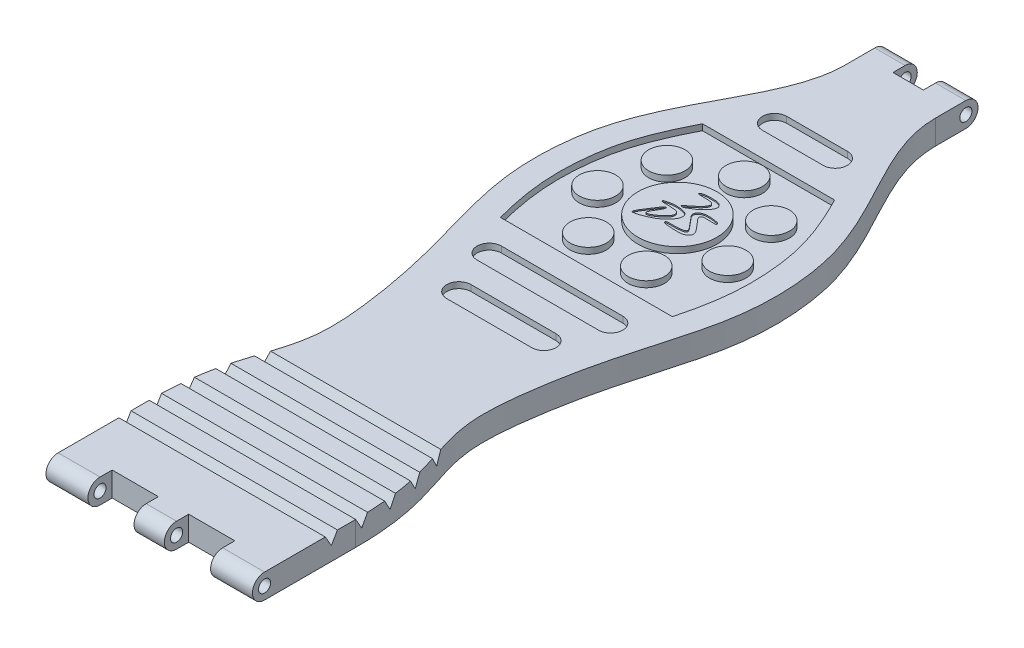
SolidWorks part; units mm, degrees
ref_plane "Front Plane" through (0, 0, 0) normal (0, 0, 1) x (1, 0, 0)
ref_plane "Top Plane" through (0, 0, 0) normal (0, 1, 0) x (1, 0, 0)
ref_plane "Right Plane" through (0, 0, 0) normal (1, 0, 0) x (0, 0, -1)
other "Configuration Table"
sketch "Sketch1" plane through (0, 0, 0) normal (0, 1, 0) x (1, 0, 0)
  line L0 (0, 0) -> (0, 152.4) construction
  line L2 (-21.59, 0) -> (21.59, 0)
  line L3 (-21.59, 0) -> (-21.59, 19.05)
  line L4 (-21.59, 19.05) -> (21.59, 19.05)
  line L5 (21.59, 0) -> (21.59, 19.05)
  line L6 (-21.59, 0) -> (21.59, 19.05) construction
  line L7 (-21.59, 19.05) -> (21.59, 0) construction
  line L8 (-9.525, 152.4) -> (9.525, 152.4)
  line L9 (-9.525, 152.4) -> (-9.525, 158.75)
  line L10 (-9.525, 158.75) -> (9.525, 158.75)
  line L11 (9.525, 152.4) -> (9.525, 158.75)
  line L12 (-9.525, 152.4) -> (9.525, 158.75) construction
  line L13 (-9.525, 158.75) -> (9.525, 152.4) construction
  spline S0 degree 3 poles (-9.525, 152.4) (-9.525, 140.7805) (-22.9495, 127.2801) (-26.9071, 91.7166) (-18.6052, 80.0483) (-14.4166, 41.5339) (-21.59, 36.242) (-21.59, 19.05) knots 0 0 0 0 0.318102 0.39652 0.741104 0.805759 1 1 1 1
  spline S1 degree 3 poles (9.525, 152.4) (9.525, 140.7805) (22.9495, 127.2801) (26.9071, 91.7166) (18.6052, 80.0483) (14.4166, 41.5339) (21.59, 36.242) (21.59, 19.05) knots 0 0 0 0 0.318102 0.39652 0.741104 0.805759 1 1 1 1
  point P7 (0, 9.525)
  point P12 (0, 155.575)
  dimension "D1" = 152.4
  dimension "D2" = 43.18
  dimension "D3" = 19.05
  dimension "D4" = 19.05
  dimension "D5" = 6.35
extrude "Boss-Extrude1" add sketch "Sketch1" against normal blind 5.08 contours S1 L8 S0 L4 | L2 L5 L4 L3 | L8 L11 L10 L9 region at (0, 0, -9.525) region at (0, 0, -84.0947) region at (0, 0, -155.575)
sketch "Sketch2" plane through (-21.59, 0, 0) normal (-1, 0, 0) x (0, 0, 1)
  line L0 (0, -5.08) -> (0, 0) construction
  circle A0 centre (0, -2.54) radius 2.54
extrude "Boss-Extrude2" add sketch "Sketch2" against normal up to surface (43.18 mm away) up to face at (21.59, -2.54, -9.525)
sketch "Sketch3" plane through (-9.525, 0, 0) normal (-1, 0, 0) x (0, 0, 1)
  line L0 (-158.75, -5.08) -> (-158.75, 0) construction
  circle A0 centre (-158.75, -2.54) radius 2.54
extrude "Boss-Extrude3" add sketch "Sketch3" against normal up to surface (19.05 mm away) up to face at (9.525, -2.54, -155.575)
sketch "Sketch4" plane through (-9.525, 0, 0) normal (-1, 0, 0) x (0, 0, 1)
  circle A0 centre (-158.75, -2.54) radius 1.27
  dimension "D1" = 2.54
extrude "Cut-Extrude1" cut sketch "Sketch4" against normal up to surface (19.05 mm away) up to face at (9.525, -2.54, -156.21)
sketch "Sketch5" plane through (-21.59, 0, 0) normal (-1, 0, 0) x (0, 0, 1)
  circle A0 centre (0, -2.54) radius 1.27
  dimension "D1" = 2.54
extrude "Cut-Extrude2" cut sketch "Sketch5" against normal up to surface (43.18 mm away) up to face at (21.59, -2.54, -8.89)
sketch "Sketch6" plane through (0, 0, 0) normal (0, 1, 0) x (1, 0, 0)
  line L0 (9.525, 161.29) -> (-9.525, 161.29) construction
  line L1 (-3.175, 2.54) -> (-12.827, 2.54)
  line L2 (-3.175, 2.54) -> (-3.175, -2.54)
  line L3 (-3.175, -2.54) -> (-12.827, -2.54)
  line L4 (-12.827, 2.54) -> (-12.827, -2.54)
  line L5 (-3.175, 2.54) -> (-12.827, -2.54) construction
  line L6 (-3.175, -2.54) -> (-12.827, 2.54) construction
  line L7 (-21.59, -2.54) -> (21.59, -2.54) construction
  line L8 (-3.175, 2.54) -> (3.175, 2.54) construction
  line L9 (3.175, 2.54) -> (12.827, 2.54)
  line L10 (3.175, 2.54) -> (3.175, -2.54)
  line L11 (3.175, -2.54) -> (12.827, -2.54)
  line L12 (12.827, 2.54) -> (12.827, -2.54)
  line L13 (3.175, 2.54) -> (12.827, -2.54) construction
  line L14 (3.175, -2.54) -> (12.827, 2.54) construction
  line L15 (3.175, 166.37) -> (-3.175, 166.37)
  line L16 (3.175, 166.37) -> (3.175, 156.21)
  line L17 (3.175, 156.21) -> (-3.175, 156.21)
  line L18 (-3.175, 166.37) -> (-3.175, 156.21)
  line L19 (3.175, 166.37) -> (-3.175, 156.21) construction
  line L20 (3.175, 156.21) -> (-3.175, 166.37) construction
  point P4 (-8.001, 0)
  point P5 (0, 2.54)
  point P6 (0, 161.29)
  point P13 (8.001, 0)
  dimension "D1" = 6.35
  dimension "D2" = 9.652
  dimension "D3" = 5.08
  dimension "D4" = 6.35
  dimension "D5" = 10.16
extrude "Cut-Extrude3" cut sketch "Sketch6" against normal up to surface (5.08 mm away) up to face at (0, -5.08, -99.2188)
sketch "Sketch7" plane through (0, 0, 0) normal (1, 0, 0) x (0, 0, -1)
  line L1 (15.24, 0) -> (13.97, -2.1997)
  line L2 (0, 0) -> (19.05, 0) construction
  line L3 (13.97, -2.1997) -> (12.7, 0)
  line L4 (12.7, 0) -> (15.24, 0)
  dimension "D1" = 2.54
  dimension "D2" = 12.7
extrude "Cut-Extrude4" cut sketch "Sketch7" against normal through all both and the other way through all
pattern_linear "LPattern1" count 5 spacing 6.35 along (0, 0, -1) of "Cut-Extrude4"
sketch "Sketch8" plane through (0, 0, 0) normal (0, 1, 0) x (1, 0, 0)
  line L0 (13.817, 127) -> (-13.817, 127)
  line L1 (17.983, 88.9) -> (-17.983, 88.9)
  line L2 (-12.7, 81.28) -> (12.7, 81.28) construction
  line L3 (-12.7, 83.82) -> (12.7, 83.82)
  line L4 (-12.7, 78.74) -> (12.7, 78.74)
  line L5 (-8.89, 71.12) -> (8.89, 71.12) construction
  line L6 (-8.89, 73.66) -> (8.89, 73.66)
  line L7 (-8.89, 68.58) -> (8.89, 68.58)
  line L8 (-6.35, 134.62) -> (6.35, 134.62) construction
  line L9 (-6.35, 137.16) -> (6.35, 137.16)
  line L10 (-6.35, 132.08) -> (6.35, 132.08)
  arc A0 (-12.7, 83.82) -> (-12.7, 78.74) centre (-12.7, 81.28) ccw
  arc A1 (12.7, 78.74) -> (12.7, 83.82) centre (12.7, 81.28) ccw
  arc A2 (-8.89, 73.66) -> (-8.89, 68.58) centre (-8.89, 71.12) ccw
  arc A3 (8.89, 68.58) -> (8.89, 73.66) centre (8.89, 71.12) ccw
  arc A4 (-6.35, 137.16) -> (-6.35, 132.08) centre (-6.35, 134.62) ccw
  arc A5 (6.35, 132.08) -> (6.35, 137.16) centre (6.35, 134.62) ccw
  spline S2 degree 3 poles (-2979.3893, -167.7654) (-176.8463, 335.583) (4.1325, 207.8677) (-4.9125, 147.4354) (-5.1756, 146.2435) (-6.1432, 142.7498) (-7.0227, 140.53) (-8.9915, 136.21) (-10.0828, 134.1078) (-12.2846, 129.9345) (-13.3956, 127.8637) (-15.4667, 123.7017) (-16.4265, 121.6114) (-17.6399, 118.4341) (-18.0068, 117.368) (-18.6494, 115.216) (-18.9221, 114.1359) (-19.61, 110.7817) (-19.8926, 108.4288) (-20.0513, 105.6351) (-20.0735, 105.0836) (-20.0997, 104.0031) (-20.1039, 103.4738) (-20.091, 101.9146) (-20.0489, 100.9131) (-19.8345, 97.9841) (-19.5747, 96.1313) (-18.8711, 92.4254) (-18.426, 90.5718) (-17.4006, 86.6995) (-16.82, 84.6813) (-15.5973, 80.3488) (-14.9558, 78.0349) (-13.7008, 72.9932) (-13.0877, 70.2658) (-12.255, 65.7755) (-11.9919, 64.2121) (-11.5046, 60.9368) (-11.2776, 59.2087) (-10.9298, 55.7161) (-10.8084, 53.9534) (-10.7771, 51.7959) (-10.7769, 51.3666) (-10.7906, 50.5129) (-10.8047, 50.0876) (-10.8691, 48.8383) (-10.9407, 48.0352) (-11.2283, 45.7083) (-11.5176, 44.2686) (-24.4626, -7.4426) (-102.0579, 68.6433) (2024.1668, -2162.2113) knots -1.484386 -1.484386 -1.484386 -1.484386 0.03125 0.03125 0.0625 0.0625 0.125 0.125 0.1875 0.1875 0.25 0.25 0.3125 0.3125 0.34375 0.34375 0.375 0.375 0.4375 0.4375 0.453125 0.453125 0.46875 0.46875 0.5 0.5 0.5625 0.5625 0.625 0.625 0.6875 0.6875 0.75 0.75 0.8125 0.8125 0.84375 0.84375 0.875 0.875 0.90625 0.90625 0.914063 0.914063 0.921875 0.921875 0.9375 0.9375 0.96875 0.96875 2.134953 2.134953 2.134953 2.134953 only from (-4.445, 152.4) to (-12.9652, 39.0961)
  spline S3 degree 3 poles (-13.817, 127) (-14.0242, 126.5945) (-14.2291, 126.1888) (-15.4667, 123.7017) (-16.4265, 121.6114) (-17.6399, 118.4341) (-18.0068, 117.368) (-18.6494, 115.216) (-18.9221, 114.1359) (-19.61, 110.7817) (-19.8926, 108.4288) (-20.0513, 105.6351) (-20.0735, 105.0836) (-20.0997, 104.0031) (-20.1039, 103.4738) (-20.091, 101.9146) (-20.0489, 100.9131) (-19.8345, 97.9841) (-19.5747, 96.1313) (-18.8871, 92.5099) (-18.4664, 90.7409) (-17.983, 88.9) knots 0.237804 0.237804 0.237804 0.237804 0.25 0.25 0.3125 0.3125 0.34375 0.34375 0.375 0.375 0.4375 0.4375 0.453125 0.453125 0.46875 0.46875 0.5 0.5 0.5625 0.5625 0.62215 0.62215 0.62215 0.62215
  spline S12 degree 3 poles (2979.3893, -167.7654) (176.8463, 335.583) (-4.1325, 207.8677) (4.9125, 147.4354) (5.1756, 146.2435) (6.1432, 142.7498) (7.0227, 140.53) (8.9915, 136.21) (10.0828, 134.1078) (12.2846, 129.9345) (13.3956, 127.8637) (15.4667, 123.7017) (16.4265, 121.6114) (17.6399, 118.4341) (18.0068, 117.368) (18.6494, 115.216) (18.9221, 114.1359) (19.61, 110.7817) (19.8926, 108.4288) (20.0513, 105.6351) (20.0735, 105.0836) (20.0997, 104.0031) (20.1039, 103.4738) (20.091, 101.9146) (20.0489, 100.9131) (19.8345, 97.9841) (19.5747, 96.1313) (18.8711, 92.4254) (18.426, 90.5718) (17.4006, 86.6995) (16.82, 84.6813) (15.5973, 80.3488) (14.9558, 78.0349) (13.7008, 72.9932) (13.0877, 70.2658) (12.255, 65.7755) (11.9919, 64.2121) (11.5046, 60.9368) (11.2776, 59.2087) (10.9298, 55.7161) (10.8084, 53.9534) (10.7771, 51.7959) (10.7769, 51.3666) (10.7906, 50.5129) (10.8047, 50.0876) (10.8691, 48.8383) (10.9407, 48.0352) (11.2283, 45.7083) (11.5176, 44.2686) (24.4626, -7.4426) (102.0579, 68.6433) (-2024.1668, -2162.2113) knots -1.484386 -1.484386 -1.484386 -1.484386 0.03125 0.03125 0.0625 0.0625 0.125 0.125 0.1875 0.1875 0.25 0.25 0.3125 0.3125 0.34375 0.34375 0.375 0.375 0.4375 0.4375 0.453125 0.453125 0.46875 0.46875 0.5 0.5 0.5625 0.5625 0.625 0.625 0.6875 0.6875 0.75 0.75 0.8125 0.8125 0.84375 0.84375 0.875 0.875 0.90625 0.90625 0.914062 0.914062 0.921875 0.921875 0.9375 0.9375 0.96875 0.96875 2.134953 2.134953 2.134953 2.134953 only from (4.445, 152.4) to (12.9652, 39.0961)
  spline S13 degree 3 poles (13.817, 127) (14.0242, 126.5945) (14.2291, 126.1888) (15.4667, 123.7017) (16.4265, 121.6114) (17.6399, 118.4341) (18.0068, 117.368) (18.6494, 115.216) (18.9221, 114.1359) (19.61, 110.7817) (19.8926, 108.4288) (20.0513, 105.6351) (20.0735, 105.0836) (20.0997, 104.0031) (20.1039, 103.4738) (20.091, 101.9146) (20.0489, 100.9131) (19.8345, 97.9841) (19.5747, 96.1313) (18.8871, 92.5099) (18.4664, 90.7409) (17.983, 88.9) knots 0.237804 0.237804 0.237804 0.237804 0.25 0.25 0.3125 0.3125 0.34375 0.34375 0.375 0.375 0.4375 0.4375 0.453125 0.453125 0.46875 0.46875 0.5 0.5 0.5625 0.5625 0.62215 0.62215 0.62215 0.62215
  point P10 (0, 81.28)
  point P17 (0, 71.12)
  point P24 (0, 134.62)
  dimension "D11" = 2.54
  dimension "D3" = 38.1
  dimension "D4" = 88.9
  dimension "D5" = 5.08
  dimension "D6" = 5.08
  dimension "D7" = 5.08
  dimension "D8" = 12.7
  dimension "D9" = 25.4
  dimension "D10" = 17.78
  dimension "D1" = 5.08
  dimension "D2" = 5.08
extrude "Cut-Extrude5" cut sketch "Sketch8" against normal blind 1.27
sketch "Sketch10" plane through (0, -1.27, 0) normal (0, 1, 0) x (1, 0, 0)
  line L0 (0, 127) -> (0, 107.95) construction
  line L1 (13.817, 127) -> (-13.817, 127) construction
  line L2 (0, 107.95) -> (0, 88.9) construction
  line L3 (-17.983, 88.9) -> (17.983, 88.9) construction
  circle A0 centre (0, 107.95) radius 13.97 construction
  circle A1 centre (0, 121.92) radius 3.81
  dimension "D1" = 27.94
  dimension "D2" = 7.62
extrude "Boss-Extrude4" add sketch "Sketch10" along normal up to surface (1.27 mm away) up to face at (0, 0, -17.145)
ref_axis "Axis1" through (0, -1.27, -107.95) along (0, 1, 0)
pattern_circular "CirPattern1" count 7 over 360 about axis through (0, -1.27, -107.95) along (0, 1, 0) of "Boss-Extrude4"
sketch "Sketch11" plane through (0, -1.27, 0) normal (0, 1, 0) x (1, 0, 0)
  circle A0 centre (0, 107.95) radius 8.255
  dimension "D1" = 16.51
extrude "Boss-Extrude5" add sketch "Sketch11" along normal up to surface (1.27 mm away) up to face at (0, 0, -17.145)
sketch "Sketch13" plane through (0, 0, 0) normal (0, 1, 0) x (1, 0, 0)
  line L0 (2.189, 110.8352) -> (135.5223, 110.8352) construction
  line L1 (-4.7639, 104.9913) -> (-2.9762, 107.7207)
  spline S0 degree 3 poles (-1.5118, 114.0219) (-1.4421, 114.1685) (-0.9455, 114.3858) (-0.0135, 114.4891) (1.0558, 114.4891) (2.0477, 114.3932) (2.7056, 114.0722) (3.0994, 113.3783) (2.7383, 112.4905) (2.047, 111.6691) (1.2567, 110.933) (0.4306, 110.4557) (-0.2135, 110.0539) (-0.7571, 109.8009) (-1.0928, 109.8229) (-1.1827, 109.8991) knots 0 0 0 0 0.042326 0.13724 0.264506 0.335188 0.412965 0.455949 0.542825 0.649198 0.759646 0.837282 0.91245 0.970561 1 1 1 1
  spline S1 degree 3 poles (-1.5118, 114.0219) (-1.5295, 113.9845) (-1.5573, 113.824) (-1.0288, 113.8407) (-0.5399, 113.7816) (0.2213, 113.8271) (0.9351, 113.7381) (1.5336, 113.632) (1.8798, 113.1647) (1.5642, 112.4988) (1.1006, 111.9536) (0.4533, 111.3495) (-0.1661, 110.8633) (-0.7411, 110.385) (-1.0916, 110.1712) (-1.2246, 109.9764) (-1.218, 109.9291) (-1.1827, 109.8991) knots 0 0 0 0 0.011373 0.060874 0.126759 0.224901 0.323556 0.397977 0.434798 0.518924 0.62848 0.708164 0.839679 0.91754 0.981655 0.988925 1 1 1 1
  spline S2 degree 3 poles (-4.0381, 108.868) (-4.0409, 108.9843) (-3.36, 109.1903) (-2.6615, 109.343) (-1.4635, 109.4627) (-0.3391, 109.2894) (0.8414, 108.9393) (1.0473, 107.8102) (0.6248, 106.9607) (-0.101, 106.2489) (-0.9279, 105.3305) (-2.1379, 104.6142) (-3.3518, 104.1226) (-4.2895, 103.7796) (-4.8649, 103.6934) (-5.2364, 103.6241) (-5.3578, 103.8805) (-5.0814, 104.3794) (-5.1023, 104.4747) (-4.7639, 104.9913) knots 0 0 0 0 0.035651 0.092587 0.171081 0.257807 0.326935 0.389171 0.454193 0.508585 0.589509 0.697497 0.781321 0.850811 0.889001 0.904316 0.914583 0.937149 1 1 1 1
  spline S3 degree 3 poles (-2.9762, 107.7207) (-2.9089, 107.8271) (-2.7822, 107.9483) (-2.6036, 108.0702) (-2.4627, 108.0991) (-2.3116, 107.9763) (-2.3905, 107.6566) (-2.6246, 107.1553) (-3.0601, 106.4363) (-3.4749, 105.7713) (-3.6685, 105.3061) (-3.7083, 104.88) (-3.0246, 105.0224) (-2.5317, 105.3264) (-1.8156, 105.7718) (-1.2111, 106.3304) (-0.6929, 106.858) (-0.3311, 107.3259) (-0.2918, 107.7881) (-0.4264, 108.4649) (-1.4839, 108.5803) (-2.4157, 108.6591) (-3.2071, 108.6662) (-3.6799, 108.6418) (-3.9644, 108.6667) (-4.0362, 108.7898) (-4.0381, 108.868) knots 0 0 0 0 0.028901 0.040122 0.05025 0.059683 0.079637 0.116476 0.193844 0.272447 0.293654 0.317292 0.348338 0.411714 0.470913 0.537541 0.602808 0.644437 0.668799 0.709518 0.788261 0.872675 0.94124 0.966275 0.986327 1 1 1 1
  spline S4 degree 3 poles (5.9171, 110.2609) (5.8974, 110.415) (5.7774, 110.6467) (5.1885, 110.7293) (4.5024, 110.8824) (3.5978, 110.9037) (2.7444, 110.8738) (2.0162, 110.5477) (1.6091, 110.0923) (1.4487, 109.4119) (2.0995, 108.6454) (2.7732, 107.7583) (3.4813, 107.0268) (3.866, 106.4857) (4.0233, 106.1213) (3.8689, 105.8808) (3.5188, 105.7019) (2.8314, 105.6248) (1.8945, 105.5322) (1.0181, 105.557) (0.4054, 105.5553) (0.1075, 105.478) (-0.0748, 105.2311) (0.4169, 104.9671) (0.9806, 104.9339) (1.8717, 104.8398) (2.871, 104.8642) (3.8472, 104.7899) (4.6144, 105.0934) (5.0467, 105.4347) (5.2361, 105.7908) (5.2894, 106.1821) (5.0968, 106.6365) (4.8026, 107.0862) (4.4548, 107.4389) (4.2094, 107.7821) (3.9322, 108.1043) (3.5674, 108.4976) (3.2306, 108.9226) (2.9071, 109.3099) (2.7015, 109.6882) (2.9328, 110.0781) (3.4295, 110.2127) (4.1664, 110.1262) (4.9447, 110.1813) (5.5436, 110.1349) (5.8115, 110.1708) (5.9171, 110.2609) (5.8974, 110.415) (5.7774, 110.6467) knots -0.013676 -0.007513 -0.004089 0 0.007968 0.022841 0.058736 0.08767 0.120199 0.151122 0.171586 0.184517 0.223593 0.26853 0.310885 0.3315 0.343293 0.34938 0.360543 0.384926 0.423995 0.46313 0.480211 0.490538 0.495988 0.50844 0.53378 0.56595 0.602255 0.644043 0.670076 0.690282 0.702523 0.713089 0.732151 0.754234 0.771685 0.785767 0.800094 0.817888 0.844235 0.858518 0.874128 0.886178 0.901952 0.927093 0.966949 0.986324 0.992487 0.995911 1 1.007968 1.022841 1.058736 only from (5.8979, 110.3745) to (5.8979, 110.3745)
extrude "Cut-Extrude6" cut sketch "Sketch13" against normal blind 0.254
scale "Scale1" scale about centroid uniform scaling yes scale factor 1.5
